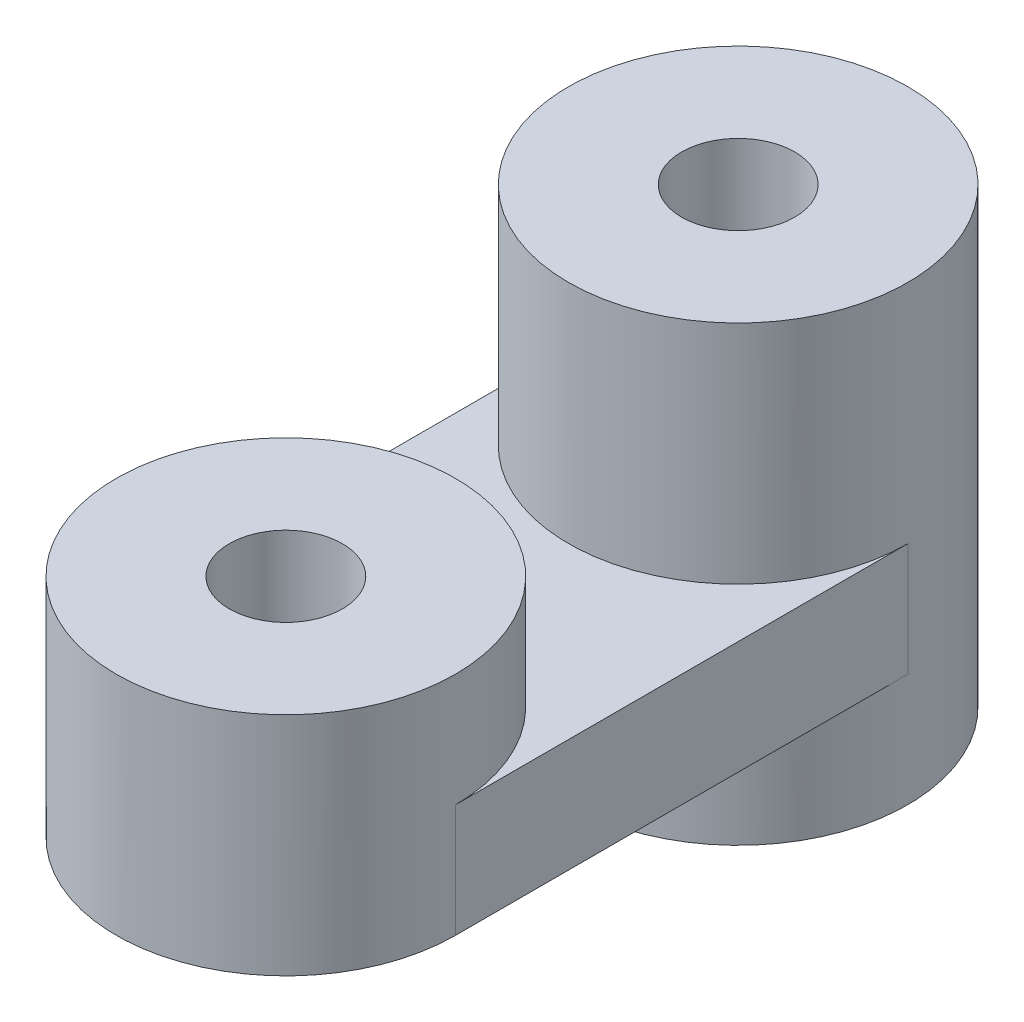
SolidWorks part; units mm, degrees
ref_plane "Alzado" through (0, 0, 0) normal (0, 0, 1) x (1, 0, 0)
ref_plane "Planta" through (0, 0, 0) normal (0, 1, 0) x (1, 0, 0)
ref_plane "Vista lateral" through (0, 0, 0) normal (1, 0, 0) x (0, 0, -1)
sketch "Croquis1" plane through (0, 0, 0) normal (0, 1, 0) x (1, 0, 0)
  line L0 (0, 0) -> (0, 20) construction
  line L1 (-7.5, 0) -> (-7.5, 20)
  line L2 (7.5, 0) -> (7.5, 20)
  arc A0 (-7.5, 0) -> (7.5, 0) centre (0, 0) ccw
  arc A1 (7.5, 20) -> (-7.5, 20) centre (0, 20) ccw
  circle A2 centre (0, 20) radius 2.5
  circle A3 centre (0, 0) radius 2.5
  point P3 (0, 10)
  point P8 (0, 27.5)
  point P9 (0, -7.5)
  dimension "D1" = 7.5
  dimension "D3" = 5
  dimension "D4" = 5
  dimension "D2" = 35
extrude "Saliente-Extruir1" add sketch "Croquis1" along normal blind 5
sketch "Croquis2" plane through (0, 5, 0) normal (0, 1, 0) x (1, 0, 0)
  line L2 (7.5, 0) -> (7.5, 20)
  line L3 (-7.5, 20) -> (-7.5, 0)
  circle A0 centre (0, 0) radius 2.5
  circle A1 centre (0, 0) radius 7.5
  arc A2 (-7.5, 0) -> (7.5, 0) centre (0, 0) ccw
  arc A3 (7.5, 20) -> (-7.5, 20) centre (0, 20) ccw
  arc A4 (-7.5, 0) -> (7.5, 0) centre (0, 0) ccw
  arc A5 (7.5, 20) -> (-7.5, 20) centre (0, 20) ccw
  circle A6 centre (0, 20) radius 2.5
  circle A7 centre (0, 20) radius 7.5
  circle M7 centre (0, 20) radius 2.5
  arc M8 (-7.5, 0) -> (7.5, 0) centre (0, 0) ccw
  arc M10 (7.5, 20) -> (-7.5, 20) centre (0, 20) ccw
  circle M12 centre (0, 0) radius 2.5
  dimension "D2" = 5
  dimension "D3" = 5
  dimension "D1" = 0
extrude "Saliente-Extruir2" add sketch "Croquis2" along normal blind 5 contours A1 M8 M12 | A7 M10 M7 region at (0, 5, 7.2879) region at (0, 5, -12.7121)
sketch "Croquis3" plane through (0, 10, 0) normal (0, 1, 0) x (1, 0, 0)
  circle A0 centre (0, 20) radius 2.5
  circle A1 centre (0, 20) radius 7.5
  circle A2 centre (0, 20) radius 7.5
  dimension "D2" = 5
  dimension "D1" = 0
extrude "Saliente-Extruir3" add sketch "Croquis3" along normal blind 5
sketch "Croquis4" plane through (0, 0, 0) normal (0, -1, 0) x (1, 0, 0)
  line L2 (-7.5, 0) -> (-7.5, -20)
  line L3 (7.5, -20) -> (7.5, 0)
  line L4 (-7.5, 0) -> (-7.5, -20)
  line L5 (7.5, -20) -> (7.5, 0)
  circle A0 centre (0, -20) radius 7.5
  circle A1 centre (0, -20) radius 2.5
  arc A2 (7.5, 0) -> (-7.5, 0) centre (0, 0) ccw
  arc A3 (-7.5, -20) -> (7.5, -20) centre (0, -20) ccw
  arc A4 (7.5, 0) -> (-7.5, 0) centre (0, 0) ccw
  arc A5 (-7.5, -20) -> (7.5, -20) centre (0, -20) ccw
  arc M8 (-7.5, -20) -> (7.5, -20) centre (0, -20) ccw
  circle M10 centre (0, -20) radius 2.5
  dimension "D2" = 5
  dimension "D1" = 0
extrude "Saliente-Extruir4" add sketch "Croquis4" along normal blind 5 contours A0 M8 M10 region at (0, 0, -12.7121)
